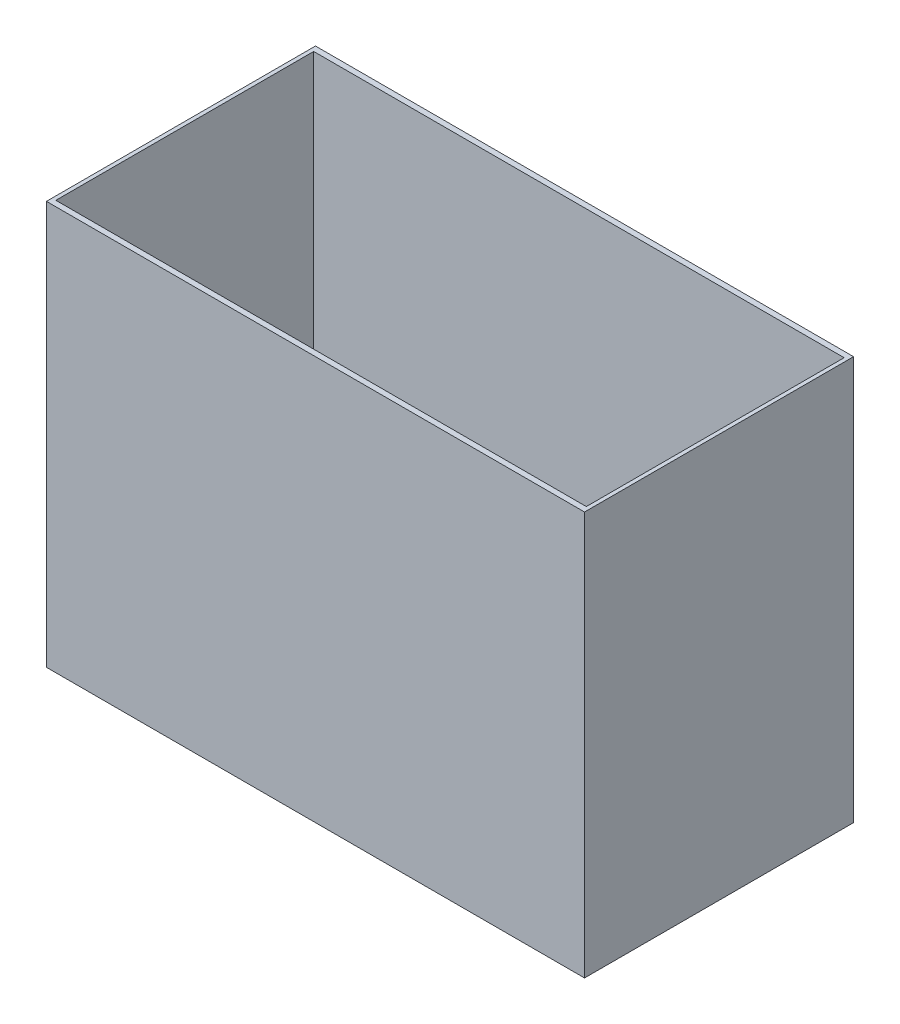
SolidWorks part; units mm, degrees
ref_plane "Front Plane" through (0, 0, 0) normal (0, 0, 1) x (1, 0, 0)
ref_plane "Top Plane" through (0, 0, 0) normal (0, 1, 0) x (1, 0, 0)
ref_plane "Right Plane" through (0, 0, 0) normal (1, 0, 0) x (0, 0, -1)
other "Bounding Box"
ref_plane "Default Plane" through (-292.1, 0, -139.7) normal (0, 1, 0) x (1, 0, 0)
sketch "Sketch1" plane through (0, 0, 0) normal (0, 1, 0) x (1, 0, 0)
  line L0 (-292.1, 0) -> (292.1, 0) construction
  line L1 (-292.1, 139.7) -> (292.1, 139.7)
  line L2 (-292.1, 139.7) -> (-292.1, -139.7)
  line L3 (-292.1, -139.7) -> (292.1, -139.7)
  line L4 (292.1, 139.7) -> (292.1, -139.7)
  line L5 (0, 139.7) -> (0, -139.7) construction
  point P8 (0, 0)
  dimension "D1" = 584.2
  dimension "D2" = 279.4
extrude "Boss-Extrude1" add sketch "Sketch1" along normal blind 6.35
sketch "Sketch2" plane through (0, 6.35, 0) normal (0, 1, 0) x (1, 0, 0)
  line L0 (-245.9259, -63.5) -> (-55.3589, -63.5) construction
  line L1 (-241.3, -120.6497) -> (-152.4, -120.6497)
  line L2 (-241.3, -120.6497) -> (-241.3, -101.5997)
  line L3 (-241.3, -101.5997) -> (-152.4, -101.5997)
  line L4 (-152.4, -120.6497) -> (-152.4, -101.5997)
  line L5 (-241.3, -120.6497) -> (-152.4, -101.5997) construction
  line L6 (-241.3, -101.5997) -> (-152.4, -120.6497) construction
  line L7 (-292.1, 139.7) -> (-292.1, -139.7) construction
  line L8 (-292.1, 0) -> (292.1, 0) construction
  line L9 (292.1, -139.7) -> (292.1, 139.7) construction
  line L10 (0, 0) -> (0, 121.6784) construction
  line L11 (241.3, -101.5997) -> (152.4, -120.6497) construction
  line L12 (241.3, -120.6497) -> (152.4, -101.5997) construction
  line L13 (152.4, -120.6497) -> (152.4, -101.5997)
  line L14 (241.3, -101.5997) -> (152.4, -101.5997)
  line L15 (241.3, -120.6497) -> (241.3, -101.5997)
  line L16 (241.3, -120.6497) -> (152.4, -120.6497)
  point P0 (-196.85, -111.1247)
  point P17 (196.85, -111.1247)
  dimension "D1" = 19.05
  dimension "D2" = 88.9
  dimension "D3" = 38.0997
  dimension "D4" = 50.8
  dimension "D5" = 63.5
extrude "Boss-Extrude2" [suppressed] add sketch "Sketch2" along normal blind 304.8 separate body contours L2 L1 L4 L3
pattern_linear "LPattern1" [suppressed] count 2 spacing 304.8 of bodies 101
pattern_linear "LPattern2" [suppressed] count 2 spacing 215.9 of bodies 101
sketch "Sketch3" plane through (0, 0, 0) normal (0, 1, 0) x (1, 0, 0)
  line L1 (-304.8, -152.4) -> (304.8, -152.4)
  line L2 (-304.8, -152.4) -> (-304.8, 152.4)
  line L3 (-304.8, 152.4) -> (304.8, 152.4)
  line L4 (304.8, -152.4) -> (304.8, 152.4)
  line L5 (-304.8, -152.4) -> (304.8, 152.4) construction
  line L6 (-304.8, 152.4) -> (304.8, -152.4) construction
  line L7 (-300.482, -146.05) -> (300.482, -146.05)
  line L8 (-300.482, -146.05) -> (-300.482, 146.05)
  line L9 (-300.482, 146.05) -> (300.482, 146.05)
  line L10 (300.482, -146.05) -> (300.482, 146.05)
  line L11 (-300.482, -146.05) -> (300.482, 146.05) construction
  line L12 (-300.482, 146.05) -> (300.482, -146.05) construction
  point P0 (0, 0)
  point P6 (0, 0)
  dimension "D1" = 609.6
  dimension "D2" = 304.8
  dimension "D3" = 292.1
  dimension "D4" = 600.964
extrude "Boss-Extrude3" add sketch "Sketch3" along normal blind 457.2 separate body
sketch "Sketch4" plane through (0, 6.35, 0) normal (0, 1, 0) x (1, 0, 0)
  line L0 (292.1, -139.7) -> (292.1, 139.7) construction
  line L1 (238.8561, 120.65) -> (261.8611, 120.65) construction
  line L2 (273.05, 95.4723) -> (273.05, 121.6668) construction
  line L3 (292.1, 139.7) -> (-292.1, 139.7) construction
  circle A3 centre (252.0119, 99.6119) radius 21.0381
  dimension "D1" = 42.0762
  dimension "D2" = 19.05
  dimension "D3" = 19.05
extrude "Cut-Extrude1" cut sketch "Sketch4" against normal through all
sketch "Sketch7" plane through (0, 6.35, 0) normal (0, 1, 0) x (1, 0, 0)
  line L0 (292.1, 0) -> (49.4912, 0) construction
  line L1 (292.1, -139.7) -> (292.1, 139.7) construction
  circle A0 centre (190.5, 0) radius 4 construction
  circle A1 centre (190.5, 0) radius 2.7781
  dimension "D1" = 8
  dimension "D2" = 5.5562
  dimension "D3" = 101.6
extrude "Cut-Extrude3" [suppressed] cut sketch "Sketch7" against normal through all
sketch "Sketch8" [suppressed] plane through (0, 6.35, 0) normal (0, 1, 0) x (1, 0, 0)
  circle A0 centre (94.9, -12.8415) radius 1.9844 construction
  circle A1 centre (146.1, -12.8415) radius 1.9844 construction
  circle A2 centre (146.1, 12.8415) radius 1.9844 construction
  circle A3 centre (94.9, 12.8415) radius 1.9844 construction
  circle A4 centre (94.9, -12.8415) radius 1.9844
  circle A5 centre (146.1, -12.8415) radius 1.9844
  circle A6 centre (146.1, 12.8415) radius 1.9844
  circle A7 centre (94.9, 12.8415) radius 1.9844
extrude "Cut-Extrude4" [suppressed] cut sketch "Sketch8" against normal through all
sketch "Sketch9" plane through (0, 0, 0) normal (0, -1, 0) x (1, 0, 0)
  circle A1 centre (190.5, 0) radius 6.35
  circle A2 centre (146.1, 12.8415) radius 6.35
  circle A3 centre (94.9, 12.8415) radius 6.35
  circle A4 centre (94.9, -12.8415) radius 6.35
  circle A5 centre (146.1, -12.8415) radius 6.35
sketch "Sketch11" plane through (0, 0, 0) normal (0, -1, 0) x (1, 0, 0)
  line L0 (-292.1, 139.7) -> (292.1, 139.7) construction
  line L1 (215.9, 139.7) -> (165.1, 139.7)
  line L2 (215.9, 139.7) -> (215.9, 136.525)
  line L3 (215.9, 136.525) -> (165.1, 136.525)
  line L4 (165.1, 139.7) -> (165.1, 136.525)
  line L5 (292.1, 139.7) -> (292.1, -139.7) construction
  dimension "D1" = 3.175
  dimension "D2" = 50.8
  dimension "D3" = 76.2
extrude "Cut-Extrude6" cut sketch "Sketch11" against normal through all
mirror "Mirror2" about plane through (0, 0, 0) normal (0, 0, 1) of "Cut-Extrude1", "Cut-Extrude6"
sketch "Sketch12" plane through (0, 6.35, 0) normal (0, 1, 0) x (1, 0, 0)
  line L0 (292.1, -17.78) -> (285.75, -17.78) construction
  line L1 (292.1, -43.18) -> (285.75, -43.18) construction
  line L2 (285.75, -43.18) -> (285.75, -17.78) construction
  line L3 (292.1, -78.74) -> (285.75, -78.74) construction
  line L4 (292.1, -104.14) -> (285.75, -104.14) construction
  line L5 (285.75, -78.74) -> (285.75, -104.14) construction
  line L6 (292.1, -17.78) -> (285.75, -17.78)
  line L7 (292.1, -43.18) -> (285.75, -43.18)
  line L8 (285.75, -43.18) -> (285.75, -17.78)
  line L9 (292.1, -78.74) -> (285.75, -78.74)
  line L10 (292.1, -104.14) -> (285.75, -104.14)
  line L11 (285.75, -78.74) -> (285.75, -104.14)
  line L12 (292.1, 0) -> (-292.1, 0) construction
  line L13 (285.75, 78.74) -> (285.75, 104.14)
  line L14 (292.1, 104.14) -> (285.75, 104.14)
  line L15 (292.1, 78.74) -> (285.75, 78.74)
  line L16 (285.75, 43.18) -> (285.75, 17.78)
  line L17 (292.1, 43.18) -> (285.75, 43.18)
  line L18 (292.1, 17.78) -> (285.75, 17.78)
  line L19 (292.1, -139.7) -> (292.1, 139.7) construction
  line L20 (292.1, -104.14) -> (292.1, -78.74)
  line L21 (292.1, -43.18) -> (292.1, -17.78)
  line L22 (292.1, 17.78) -> (292.1, 43.18)
  line L23 (292.1, 78.74) -> (292.1, 104.14)
  line L24 (-292.1, 139.7) -> (-292.1, -139.7) construction
  line L25 (0, 0) -> (0, 121.3012) construction
  line L26 (-292.1, 78.74) -> (-292.1, 104.14)
  line L27 (-292.1, 17.78) -> (-292.1, 43.18)
  line L28 (-292.1, -43.18) -> (-292.1, -17.78)
  line L29 (-292.1, -104.14) -> (-292.1, -78.74)
  line L30 (-292.1, 17.78) -> (-285.75, 17.78)
  line L31 (-292.1, 43.18) -> (-285.75, 43.18)
  line L32 (-285.75, 43.18) -> (-285.75, 17.78)
  line L33 (-292.1, 78.74) -> (-285.75, 78.74)
  line L34 (-292.1, 104.14) -> (-285.75, 104.14)
  line L35 (-285.75, 78.74) -> (-285.75, 104.14)
  line L36 (-285.75, -78.74) -> (-285.75, -104.14)
  line L37 (-292.1, -104.14) -> (-285.75, -104.14)
  line L38 (-292.1, -78.74) -> (-285.75, -78.74)
  line L39 (-285.75, -43.18) -> (-285.75, -17.78)
  line L40 (-292.1, -43.18) -> (-285.75, -43.18)
  line L41 (-292.1, -17.78) -> (-285.75, -17.78)
extrude "Cut-Extrude7" cut sketch "Sketch12" against normal through all
sketch "Sketch13" plane through (0, 6.35, 0) normal (0, 1, 0) x (1, 0, 0)
  line L0 (252.0119, -99.6119) -> (133.5003, -46.1866) construction
  line L1 (210.6176, 12.194) -> (133.5003, -46.1866) construction
  line L2 (252.0119, 99.6119) -> (210.6176, 12.194) construction
  line L3 (257.6906, -66.7163) -> (23.4514, -66.7163) construction
  circle A0 centre (252.0119, -99.6119) radius 21.0381 construction
  circle A1 centre (252.0119, -99.6119) radius 21.0381 construction
  circle A2 centre (133.5003, -46.1866) radius 21.0381
  circle A3 centre (210.6176, 12.194) radius 21.0381
  circle A4 centre (252.0119, 99.6119) radius 21.0381 construction
  circle A5 centre (252.0119, 99.6119) radius 21.0381 construction
  circle A6 centre (210.6176, 12.194) radius 55.7022 construction
  point P9 (135.4762, -42.0037)
  point P11 (0, 0)
  point P15 (133.5003, -46.1866)
  dimension "D1" = 129.9972
  dimension "D3" = 111.4044
  dimension "D2" = 96.7232
  dimension "D4" = 96.7232
extrude "Cut-Extrude8" cut sketch "Sketch13" against normal through all
sketch "Sketch14" plane through (0, 6.35, 0) normal (0, 1, 0) x (1, 0, 0)
  circle A1 centre (45.3035, 4.219) radius 4.7113 construction
  circle A2 centre (45.3035, 4.219) radius 2.7781
  dimension "D1" = 5.5562
extrude "Cut-Extrude9" cut sketch "Sketch14" against normal through all
sketch "Sketch15" plane through (0, 0, 0) normal (0, -1, 0) x (1, 0, 0)
  line L0 (88.9, -38.1) -> (88.9, -57.15) construction
  line L1 (88.9, -57.15) -> (95.25, -57.15) construction
  line L2 (95.25, -57.15) -> (95.25, -38.1) construction
  line L3 (95.25, -38.1) -> (88.9, -38.1) construction
  line L4 (88.9, 57.15) -> (88.9, 31.75) construction
  line L5 (88.9, 31.75) -> (95.25, 31.75) construction
  line L6 (95.25, 31.75) -> (95.25, 57.15) construction
  line L7 (95.25, 57.15) -> (88.9, 57.15) construction
  line L8 (88.9, -38.1) -> (88.9, -57.15) construction
  line L9 (88.9, -57.15) -> (95.25, -57.15) construction
  line L10 (95.25, -57.15) -> (95.25, -38.1) construction
  line L11 (95.25, -38.1) -> (88.9, -38.1) construction
  line L12 (88.9, 57.15) -> (88.9, 31.75) construction
  line L13 (88.9, 31.75) -> (95.25, 31.75) construction
  line L14 (95.25, 31.75) -> (95.25, 57.15) construction
  line L15 (95.25, 57.15) -> (88.9, 57.15) construction
  line L16 (88.773, -37.973) -> (88.773, -57.277)
  line L17 (88.773, -57.277) -> (95.377, -57.277)
  line L18 (95.377, -57.277) -> (95.377, -37.973)
  line L19 (95.377, -37.973) -> (88.773, -37.973)
  line L20 (88.773, 57.277) -> (88.773, 31.623)
  line L21 (88.773, 31.623) -> (95.377, 31.623)
  line L22 (95.377, 31.623) -> (95.377, 57.277)
  line L23 (95.377, 57.277) -> (88.773, 57.277)
  dimension "D1" = 0.127
  dimension "D2" = 0.127
extrude "Cut-Extrude10" cut sketch "Sketch15" against normal through all
sketch "Sketch16" plane through (0, 0, 0) normal (0, -1, 0) x (1, 0, 0)
  line L0 (-63.5, -66.675) -> (-63.5, -53.975) construction
  line L1 (-63.5, -53.975) -> (-38.1, -53.975) construction
  line L2 (-38.1, -66.675) -> (-38.1, -53.975) construction
  line L3 (-63.5, -66.675) -> (-38.1, -66.675) construction
  line L4 (-215.9, -66.675) -> (-215.9, -53.975) construction
  line L5 (-241.3, -53.975) -> (-215.9, -53.975) construction
  line L6 (-241.3, -66.675) -> (-241.3, -53.975) construction
  line L7 (-241.3, -66.675) -> (-215.9, -66.675) construction
  line L8 (-63.5, -66.675) -> (-63.5, -53.975)
  line L9 (-63.5, -53.975) -> (-38.1, -53.975)
  line L10 (-38.1, -66.675) -> (-38.1, -53.975)
  line L11 (-63.5, -66.675) -> (-38.1, -66.675)
  line L12 (-215.9, -66.675) -> (-215.9, -53.975)
  line L13 (-241.3, -53.975) -> (-215.9, -53.975)
  line L14 (-241.3, -66.675) -> (-241.3, -53.975)
  line L15 (-241.3, -66.675) -> (-215.9, -66.675)
  line L16 (-292.1, 0) -> (-84.0789, 0) construction
  line L18 (-241.3, 66.675) -> (-215.9, 66.675)
  line L19 (-241.3, 66.675) -> (-241.3, 53.975)
  line L20 (-241.3, 53.975) -> (-215.9, 53.975)
  line L21 (-215.9, 66.675) -> (-215.9, 53.975)
  line L22 (-63.5, 66.675) -> (-38.1, 66.675)
  line L23 (-38.1, 66.675) -> (-38.1, 53.975)
  line L24 (-63.5, 53.975) -> (-38.1, 53.975)
  line L25 (-63.5, 66.675) -> (-63.5, 53.975)
  line L26 (31.4971, -139.7) -> (31.4971, 139.7) construction
  line L27 (165.1, -139.7) -> (-292.1, -139.7) construction
  line L28 (-292.1, 139.7) -> (165.1, 139.7) construction
  point P24 (31.4971, 0)
  point P25 (0, 0)
extrude "Cut-Extrude11" cut sketch "Sketch16" against normal through all
